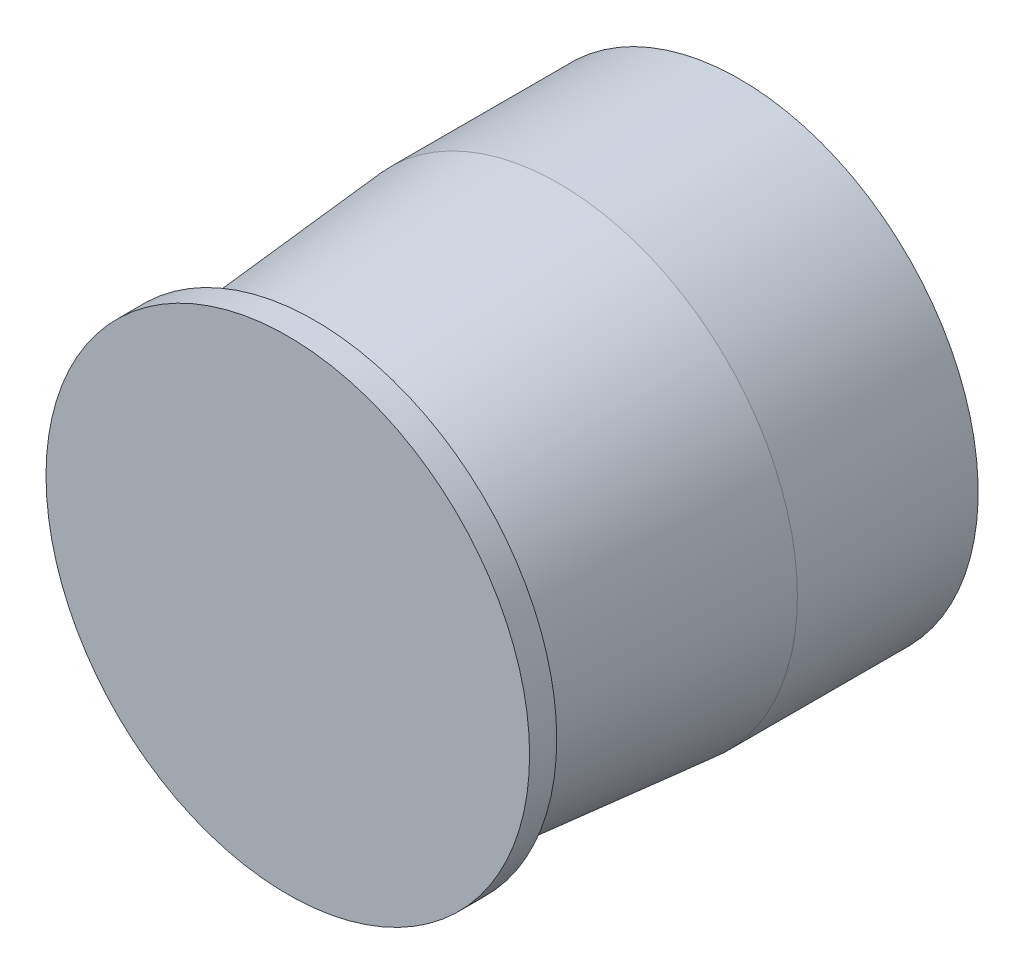
SolidWorks part; units mm, degrees
ref_plane "Front Plane" through (0, 0, 0) normal (0, 0, 1) x (1, 0, 0)
ref_plane "Top Plane" through (0, 0, 0) normal (0, 1, 0) x (1, 0, 0)
ref_plane "Right Plane" through (0, 0, 0) normal (1, 0, 0) x (0, 0, -1)
sketch "Sketch1" plane through (0, 0, 0) normal (0, 0, 1) x (1, 0, 0)
  circle A0 centre (0, 0) radius 23.75
  circle A1 centre (0, 0) radius 26.75
  dimension "D1" = 47.5
  dimension "D2" = 3
extrude "Boss-Extrude1" add sketch "Sketch1" against normal blind 30 draft 5 contours A0 region at (0, 0, 0) draft outward yes
extrude "Boss-Extrude2" add sketch "Sketch1<3>" against normal blind 3 contours A1
sketch "Sketch1<3>" plane through (0, 0, 0) normal (0, 0, 1) x (1, 0, 0) same geometry as "Sketch1"
sketch "Sketch2" plane through (0, 0, -30) normal (0, 0, -1) x (-1, 0, 0)
  circle A1 centre (0, 0) radius 26.3747
  circle A2 centre (0, 0) radius 26.3747
  dimension "D1" = 0
extrude "Boss-Extrude3" add sketch "Sketch2" along normal blind 20
